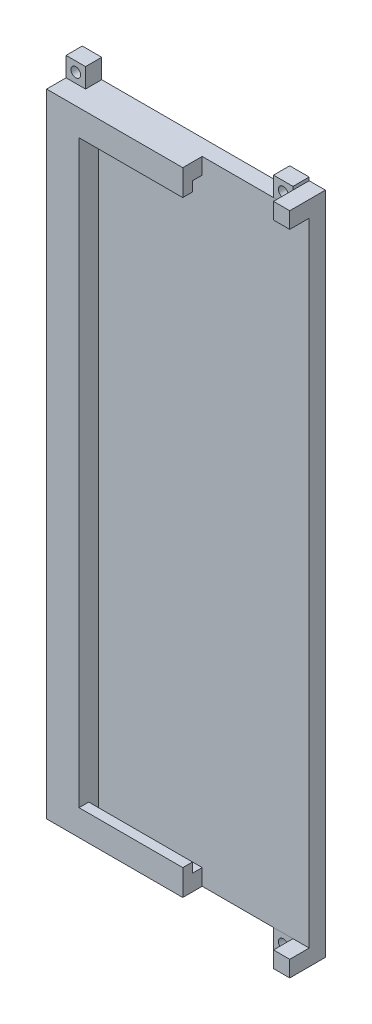
SolidWorks part; units mm, degrees
ref_plane "Front Plane" through (0, 0, 0) normal (1, 0, 0) x (0, 1, 0)
ref_plane "Top Plane" through (0, 0, 0) normal (0, 0, 1) x (0, 1, 0)
ref_plane "Right Plane" through (0, 0, 0) normal (0, 1, 0) x (-1, 0, 0)
sketch "Sketch1" plane through (0, 0, 0) normal (0, 0, 1) x (0, 1, 0)
  line L2 (-97.5, 5) -> (-97.5, 75)
  line L3 (-97.5, 75) -> (97.5, 75)
  line L4 (97.5, 5) -> (97.5, 75)
  line L5 (-102.5, 0) -> (-102.5, 5)
  line L6 (-102.5, 5) -> (-97.5, 5)
  line L7 (0, 75) -> (0, 0) construction
  line L9 (102.5, 0) -> (102.5, 5)
  line L10 (102.5, 5) -> (97.5, 5)
  line L11 (-102.5, 0) -> (102.5, 0)
  dimension "D1" = 195
  dimension "D2" = 5
  dimension "D3" = 5
  dimension "D4" = 75
extrude "Boss-Extrude1" add sketch "Sketch1" along normal blind 5
sketch "Sketch4" plane through (0, 0, 5) normal (0, 0, 1) x (1, 0, 0)
  line L0 (-75, 97.5) -> (-75, -97.5)
  line L1 (-5, 97.5) -> (0, 97.5)
  line L2 (-5, 97.5) -> (-5, 102.5)
  line L3 (-5, 102.5) -> (0, 102.5)
  line L4 (0, 97.5) -> (0, 102.5)
  line L5 (-5, -97.5) -> (0, -97.5)
  line L6 (-5, -97.5) -> (-5, -102.5)
  line L7 (-5, -102.5) -> (0, -102.5)
  line L8 (0, -97.5) -> (0, -102.5)
  line L9 (-75, 97.5) -> (-33, 97.5)
  line L11 (-65, 92.5) -> (-33, 92.5)
  line L12 (-33, 97.5) -> (-33, 92.5)
  line L13 (-75, -97.5) -> (-33, -97.5)
  line L15 (-65, -92.5) -> (-33, -92.5)
  line L16 (-33, -97.5) -> (-33, -92.5)
  line L17 (-65, 92.5) -> (-65, -92.5)
  dimension "D1" = 5
  dimension "D2" = 32
  dimension "D3" = 5
  dimension "D4" = 10
extrude "Boss-Extrude2" add sketch "Sketch4" along normal blind 6
sketch "Sketch5" plane through (-65, 0, 0) normal (1, 0, 0) x (0, 1, 0)
  line L0 (0, 11) -> (0, 5) construction
  line L1 (-92.5, 11) -> (-89.5, 11)
  line L2 (-92.5, 11) -> (-92.5, 8)
  line L3 (-92.5, 8) -> (-89.5, 8)
  line L4 (-89.5, 11) -> (-89.5, 8)
  line L5 (-92.5, 11) -> (92.5, 11) construction
  line L6 (-92.5, 5) -> (92.5, 5) construction
  line L7 (92.5, 8) -> (89.5, 8)
  line L8 (89.5, 11) -> (89.5, 8)
  line L9 (92.5, 11) -> (89.5, 11)
  line L10 (92.5, 11) -> (92.5, 8)
  dimension "D1" = 3
  dimension "D2" = 3
extrude "Boss-Extrude3" add sketch "Sketch5" along normal up to surface (32 mm away) up to face at (-33, -95, 8)
sketch "Sketch6" plane through (0, 0, 0) normal (0, 0, -1) x (1, 0, 0)
  line L0 (-40, 97.5) -> (-40, -97.5) construction
  line L1 (-5, 97.5) -> (-11, 97.5)
  line L2 (-5, 97.5) -> (-5, 103.5)
  line L3 (-5, 103.5) -> (-11, 103.5)
  line L4 (-11, 97.5) -> (-11, 103.5)
  line L5 (-75, 97.5) -> (-5, 97.5) construction
  line L6 (-5, -97.5) -> (-75, -97.5) construction
  line L7 (-75, 0) -> (0, 0) construction
  line L8 (-75, -97.5) -> (-75, 97.5) construction
  line L9 (-75, 103.5) -> (-69, 103.5)
  line L10 (-69, 97.5) -> (-69, 103.5)
  line L11 (-75, 97.5) -> (-69, 97.5)
  line L12 (-75, 97.5) -> (-75, 103.5)
  line L13 (-5, -103.5) -> (-11, -103.5)
  line L14 (-11, -97.5) -> (-11, -103.5)
  line L15 (-5, -97.5) -> (-11, -97.5)
  line L16 (-5, -97.5) -> (-5, -103.5)
  line L17 (-75, -97.5) -> (-75, -103.5)
  line L18 (-75, -97.5) -> (-69, -97.5)
  line L19 (-69, -97.5) -> (-69, -103.5)
  line L20 (-75, -103.5) -> (-69, -103.5)
  dimension "D1" = 6
extrude "Boss-Extrude4" add sketch "Sketch6" against normal blind 5 separate body
sketch "Sketch7" plane through (0, 0, 5) normal (0, 0, 1) x (1, 0, 0)
  line L0 (-11, -100.5) -> (-5, -100.5) construction
  line L1 (-11, -103.5) -> (-11, -97.5) construction
  line L2 (-5, -97.5) -> (-5, -103.5) construction
  line L3 (0, 0) -> (-65, 0) construction
  line L4 (-65, -92.5) -> (-65, 92.5) construction
  line L5 (-75, -100.5) -> (-69, -100.5) construction
  line L6 (-75, -103.5) -> (-75, -97.5) construction
  line L7 (-69, -97.5) -> (-69, -103.5) construction
  circle A0 centre (-8, -100.5) radius 1.5
  circle A1 centre (-72, -100.5) radius 1.5
  circle A2 centre (-8, 100.5) radius 1.5
  circle A3 centre (-72, 100.5) radius 1.5
  dimension "D1" = 3
  dimension "D2" = 3
extrude "Cut-Extrude1" cut sketch "Sketch7" against normal through all
